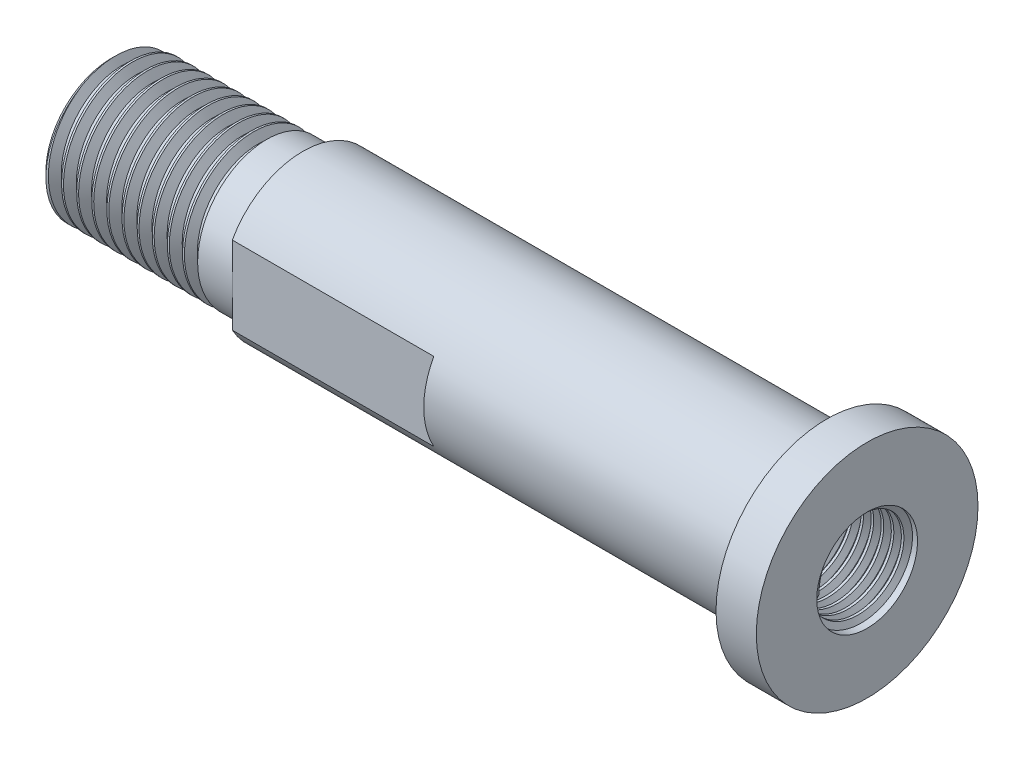
SolidWorks part; units mm, degrees
ref_plane "Спереди" through (0, 0, 0) normal (0, 0, 1) x (1, 0, 0)
ref_plane "Сверху" through (0, 0, 0) normal (0, 1, 0) x (1, 0, 0)
ref_plane "Справа" through (0, 0, 0) normal (1, 0, 0) x (0, 0, -1)
sketch "Эскиз1" plane through (0, 0, 0) normal (0, 1, 0) x (1, 0, 0)
  line L0 (-75, 0) -> (0, 0) construction
  line L1 (0, 0) -> (0, -11)
  line L2 (0, -11) -> (-4, -11)
  line L3 (-4, -11) -> (-4, -8)
  line L4 (-4, -8) -> (-56, -8)
  line L5 (-56, -7) -> (-56, -8)
  line L6 (-56, -7) -> (-75, -7)
  line L7 (-75, -7) -> (-75, 0)
  line L8 (-75, -2) -> (-52, -2)
  line L9 (-52, -2) -> (-52, -5)
  line L10 (-52, -5) -> (0, -5)
  dimension "D1" = 75
  dimension "D2" = 11
  dimension "D3" = 4
  dimension "D4" = 8
  dimension "D6" = 56
  dimension "D7" = 7
  dimension "D8" = 2
  dimension "D9" = 52
  dimension "D10" = 5
revolve "Повернуть2" add sketch "Эскиз1" angle 360 about L0 region at (-40.4129, 0, 5.838)
thread "Резьба1" pitch 1.5 method cut profile "Профиль резьбы1" start angle 0, offset 0, length 15, pitch 1.5, diameter 14
ref_plane "Плоскость1" through (-75, 0, -7) normal (0, -1, 0) x (0, 0, -1)
sketch "Профиль резьбы1" plane through (-75, 0, -7) normal (0, -1, 0) x (0, 0, -1)
  line L0 (0, 0) -> (0, 1.5) construction
  line L11 (0, 0) -> (0, 1.3125)
  line L12 (0, 1.3125) -> (-0.8119, 0.8437)
  line L13 (-0.8119, 0.8437) -> (-0.8119, 0.4687)
  line L15 (-0.8119, 0.4687) -> (0, 0)
  line L17 (-0.8119, 0.6562) -> (0, 0.6562) construction
  point P2 (0, 0)
  dimension "Pitch" = 1.5
  dimension "Profile_Angle" = 60
  dimension "Profile_Land" = 0.375
  dimension "Profile_Height" = 0.8119
chamfer "Фаска1" distance 0.5 angle 45 1 edges at (-75, 0, 7)
thread "Резьба2" pitch 1 method extrude profile "Профиль резьбы2" start angle 0, offset 0, length 15, pitch 1, diameter 10
ref_plane "Плоскость2" through (0, 0, 5) normal (0, -1, 0) x (0, 0, 1)
sketch "Профиль резьбы2" plane through (0, 0, 5) normal (0, -1, 0) x (0, 0, 1)
  line L0 (0, 0) -> (0, 1) construction
  line L11 (0, 0) -> (0, 0.875)
  line L12 (0, 0.875) -> (-0.5413, 0.5625)
  line L13 (-0.5413, 0.5625) -> (-0.5413, 0.3125)
  line L15 (-0.5413, 0.3125) -> (0, 0)
  line L17 (-0.5413, 0.4375) -> (0, 0.4375) construction
  point P2 (0, 0)
  dimension "Pitch" = 1
  dimension "Profile_Angle" = 60
  dimension "Profile_Land" = 0.25
  dimension "Profile_Height" = 0.5413
sketch "Эскиз7" plane through (-56, 0, 0) normal (-1, 0, 0) x (0, 0, 1)
  line L1 (-7, -8.5269) -> (7, -8.5269)
  line L2 (-7, -8.5269) -> (-7, 8.5269)
  line L3 (-7, 8.5269) -> (7, 8.5269)
  line L4 (7, -8.5269) -> (7, 8.5269)
  line L5 (-7, -8.5269) -> (7, 8.5269) construction
  line L6 (-7, 8.5269) -> (7, -8.5269) construction
  circle A0 centre (0, 0) radius 8
  point P0 (0, 0)
  circle M5 centre (0, 0) radius 8
  dimension "D2" = 16
  dimension "D1" = 14
extrude "Вырез-Вытянуть1" cut sketch "Эскиз7" against normal blind 20 contours L2 M5 | L4 M5 region at (-56, 0, -7.4022) region at (-56, 0, 7.4022)
